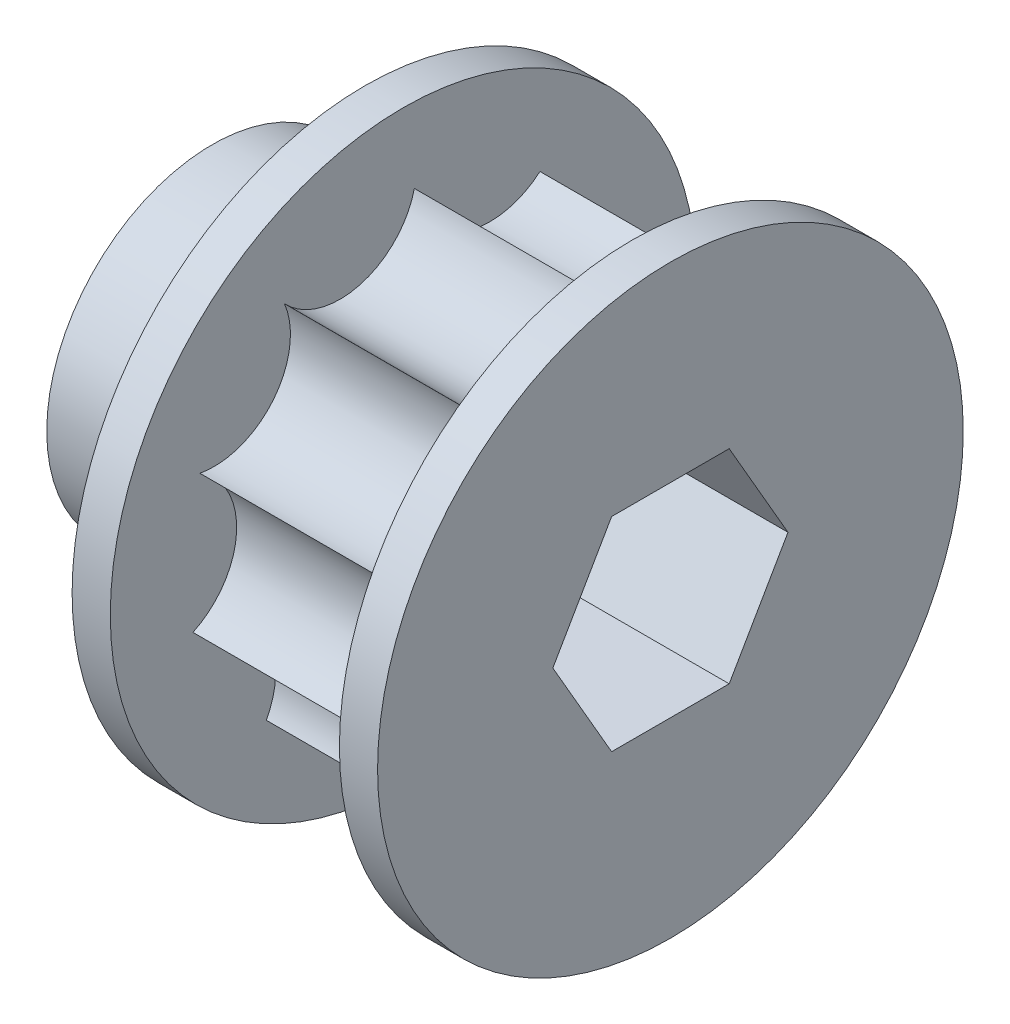
SolidWorks part; units mm, degrees
ref_plane "Front Plane" through (0, 0, 0) normal (0, 0, 1) x (1, 0, 0)
ref_plane "Top Plane" through (0, 0, 0) normal (0, 1, 0) x (1, 0, 0)
ref_plane "Right Plane" through (0, 0, 0) normal (1, 0, 0) x (0, 0, -1)
sketch "Sketch1" plane through (0, 0, 0) normal (1, 0, 0) x (0, 0, -1)
  circle A0 centre (0, 0) radius 10.3187
  dimension "D1" = 20.6375
extrude "Boss-Extrude1" add sketch "Sketch1" along normal blind 9.525
sketch "Sketch2" plane through (9.525, 0, 0) normal (1, 0, 0) x (0, 0, -1)
  circle A0 centre (0, 0) radius 18.2626
extrude "Boss-Extrude2" add sketch "Sketch2" along normal blind 19.05
sketch "Sketch3" plane through (28.575, 0, 0) normal (1, 0, 0) x (0, 0, -1)
  circle A0 centre (0, 0) radius 15.1638
extrude "Cut-Extrude1" cut sketch "Sketch3" against normal blind 14.2875 from offset 2.3813 flip side to cut offset against normal yes
sketch "Sketch4" plane through (26.1938, 0, 0) normal (-1, 0, 0) x (0, 0, 1)
  circle A0 centre (0, 0) radius 15.1638
  circle A1 centre (-12.7121, 8.267) radius 4.7625
  circle M1 centre (0, 0) radius 15.1638
extrude "Cut-Extrude2" cut sketch "Sketch4" along normal blind 14.2875 contours A1 M1 region at (26.1938, 7.0949, -10.9098)
ref_axis "Axis1" through (9.525, 0, 0) along (-1, 0, 0)
pattern_circular "CirPattern1" count 10 over 360 about axis through (9.525, 0, 0) along (-1, 0, 0) of "Cut-Extrude2"
sketch "Sketch5" plane through (0, 0, 0) normal (-1, 0, 0) x (0, 0, 1)
  line L1 (-7.3323, 0) -> (-3.6662, -6.35)
  line L2 (-3.6662, -6.35) -> (3.6662, -6.35)
  line L3 (3.6662, -6.35) -> (7.3323, 0)
  line L4 (7.3323, 0) -> (3.6662, 6.35)
  line L5 (3.6662, 6.35) -> (-3.6662, 6.35)
  line L6 (-3.6662, 6.35) -> (-7.3323, 0)
  circle A0 centre (0, 0) radius 6.35 construction
extrude "Cut-Extrude3" cut sketch "Sketch5" against normal through all
